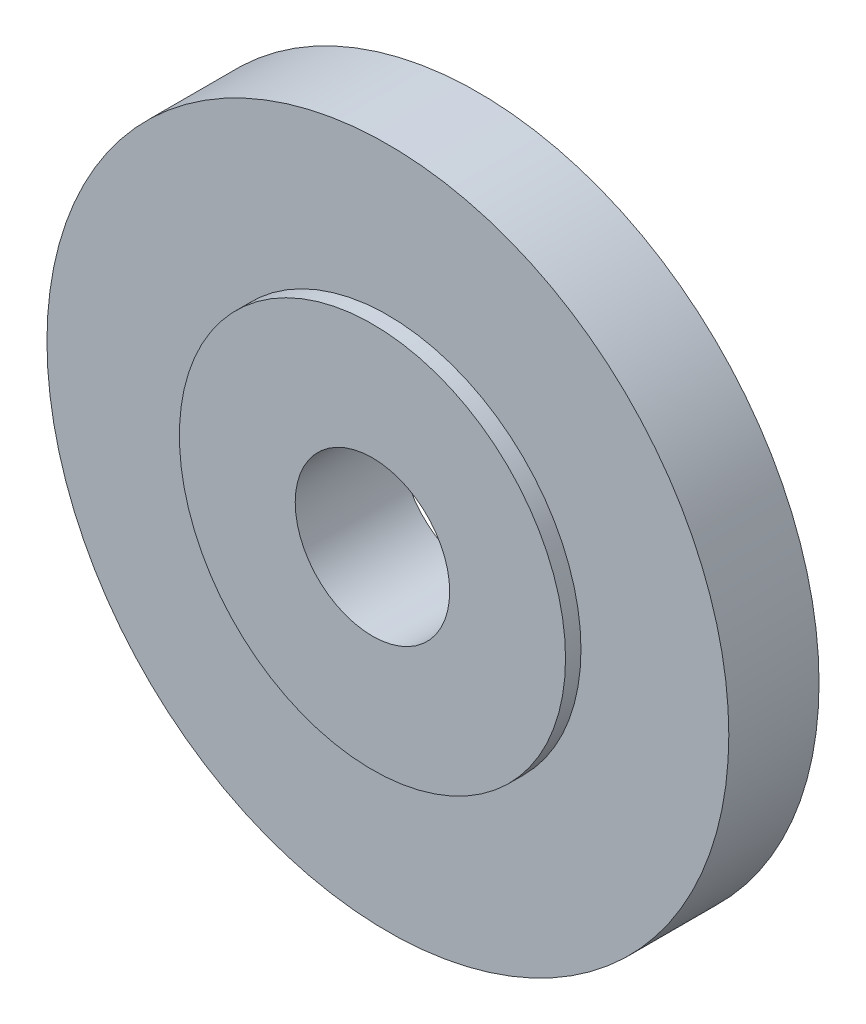
SolidWorks part; units mm, degrees
ref_plane "Front Plane" through (0, 0, 0) normal (0, 0, 1) x (1, 0, 0)
ref_plane "Top Plane" through (0, 0, 0) normal (0, 1, 0) x (1, 0, 0)
ref_plane "Right Plane" through (0, 0, 0) normal (1, 0, 0) x (0, 0, -1)
sketch "Sketch1" plane through (0, 0, 0) normal (0, 0, 1) x (1, 0, 0)
  circle A0 centre (0, 0) radius 125
  circle A1 centre (0, 0) radius 50
  dimension "D1" = 250
extrude "Boss-Extrude1" add sketch "Sketch1" along normal blind 10
sketch "Sketch2" plane through (0, 0, 0) normal (0, 0, -1) x (-1, 0, 0)
  circle A0 centre (0, 0) radius 220.72
  circle A1 centre (0, 0) radius 125
  circle A2 centre (0, 0) radius 50
  circle M3 centre (0, 0) radius 125
  circle M4 centre (0, 0) radius 50
  dimension "D1" = 441.44
  dimension "D2" = 250
extrude "Boss-Extrude2" add sketch "Sketch2" along normal blind 58.41 contours A0 M3 | M3 M4 region at (214.4771, 0, 0) region at (121.4645, 0, 0)
sketch "Sketch3" plane through (0, 0, 10) normal (0, 0, 1) x (1, 0, 0)
  circle A0 centre (-3.0905, 96.9317) radius 15
ref_axis "Axis1" through (0, 0, -58.41) along (0, 0, 1)
sketch "Sketch4" plane through (0, 0, 10) normal (0, 0, 1) x (1, 0, 0)
  line L0 (0, 0) -> (-3.0905, 96.9317) construction
  line L1 (-3.0905, 96.9317) -> (-8.2243, 257.9513) construction
ref_plane "Plane1" through (-7.0337, 220.6079, 0) normal (-0.0319, 0.9995, 0) x (0.9995, 0.0319, 0)
sketch "Sketch5" plane through (-7.0337, 220.6079, 0) normal (-0.0319, 0.9995, 0) x (0.9995, 0.0319, 0)
  circle A0 centre (0, 26.7003) radius 15
ref_plane "Plane2" through (0, 0, 0) normal (-0.9995, -0.0319, 0) x (0, 0, 1)
sketch "Sketch11" plane through (0, 0, 0) normal (-0.9995, -0.0319, 0) x (0, 0, 1)
  line L0 (-26.7003, 220.72) -> (-26.7003, 98.5714)
  line L1 (10, 96.9809) -> (-26.7003, 96.9809)
  line L2 (-26.7003, 96.9809) -> (-26.7003, 98.5714)
